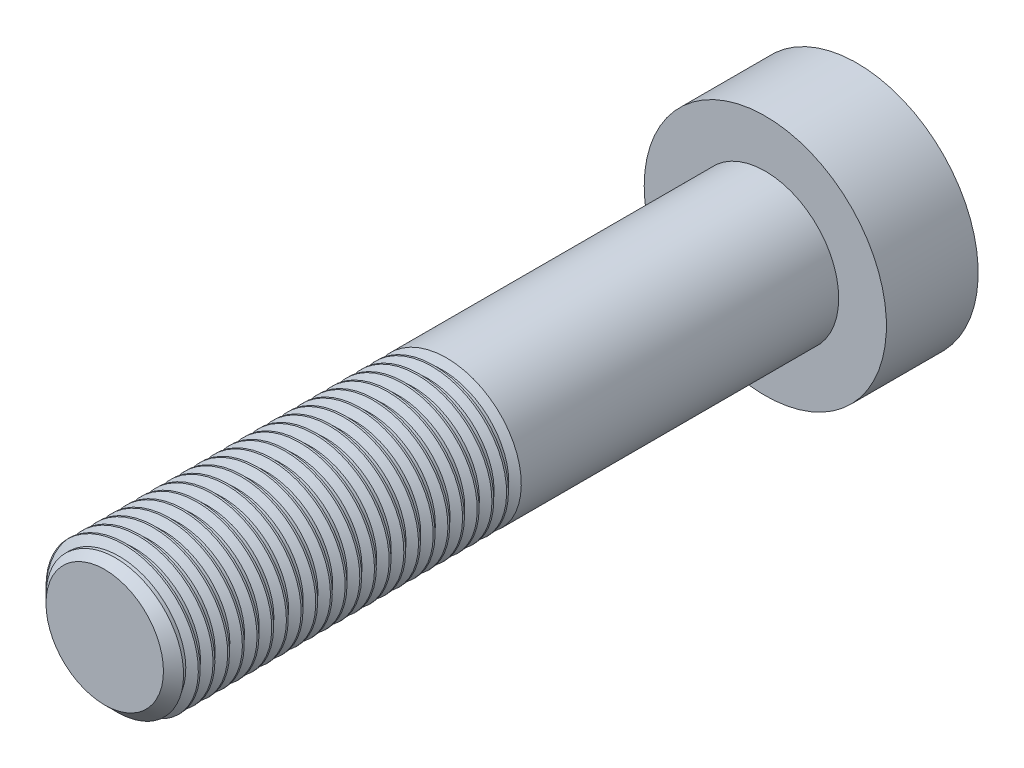
SolidWorks part; units mm, degrees
ref_plane "Спереди" through (0, 0, 0) normal (0, 0, 1) x (1, 0, 0)
ref_plane "Сверху" through (0, 0, 0) normal (0, 1, 0) x (1, 0, 0)
ref_plane "Справа" through (0, 0, 0) normal (1, 0, 0) x (0, 0, -1)
sketch "Эскиз1" plane through (0, 0, 0) normal (0, 0, 1) x (1, 0, 0)
  circle A0 centre (0, 0) radius 10
  dimension "D1" = 20
extrude "Бобышка-Вытянуть1" add sketch "Эскиз1" along normal blind 90
sketch "Эскиз2" plane through (0, 0, 0) normal (0, 0, -1) x (-1, 0, 0)
  circle A0 centre (0, 0) radius 16.5
  dimension "D1" = 33
extrude "Бобышка-Вытянуть2" add sketch "Эскиз2" along normal blind 12.5
chamfer "Фаска1" distance 2 angle 45 1 edges at (10, 0, 90)
thread "Резьба1" pitch 2 method cut profile "Профиль резьбы1" start angle 0, offset 0, length 46, pitch 2, diameter 20
ref_plane "Плоскость1" through (-10, 0, 90) normal (0, -1, 0) x (-1, 0, 0)
sketch "Профиль резьбы1" plane through (-10, 0, 90) normal (0, -1, 0) x (-1, 0, 0)
  line L0 (0, 0) -> (0, 2) construction
  line L11 (0, 0) -> (0, 1.75)
  line L12 (0, 1.75) -> (-1.0825, 1.125)
  line L13 (-1.0825, 1.125) -> (-1.0825, 0.625)
  line L15 (-1.0825, 0.625) -> (0, 0)
  line L17 (-1.0825, 0.875) -> (0, 0.875) construction
  point P2 (0, 0)
  dimension "Pitch" = 2
  dimension "Profile_Angle" = 60
  dimension "Profile_Land" = 0.5
  dimension "Profile_Height" = 1.0825
